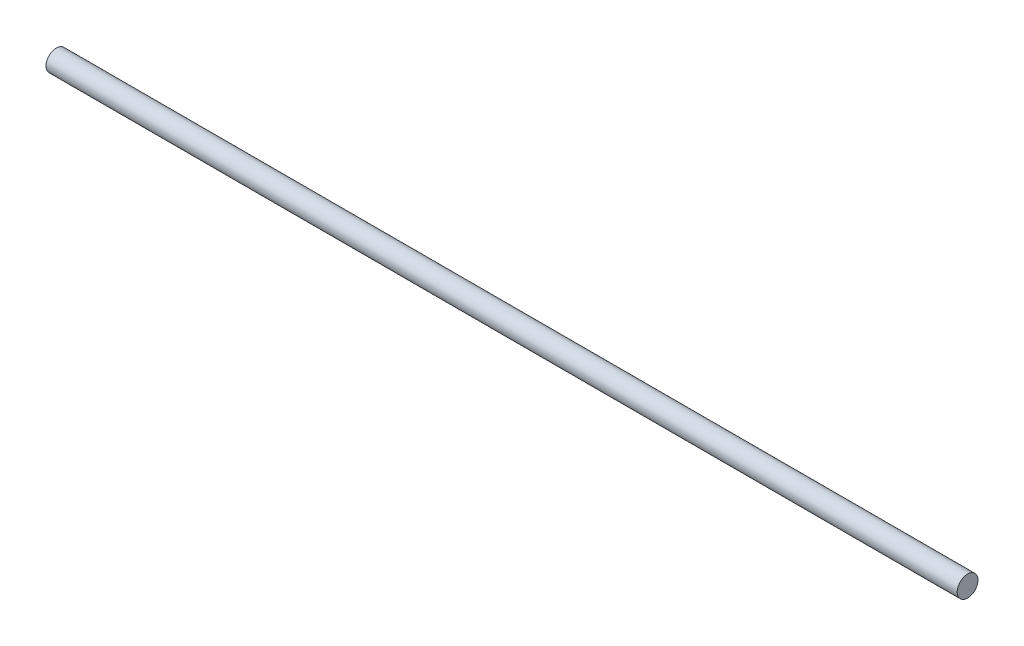
SolidWorks part; units mm, degrees
ref_plane "Front Plane" through (0, 0, 0) normal (0, 0, 1) x (1, 0, 0)
ref_plane "Top Plane" through (0, 0, 0) normal (0, 1, 0) x (1, 0, 0)
ref_plane "Right Plane" through (0, 0, 0) normal (1, 0, 0) x (0, 0, -1)
sketch "Sketch1" plane through (0, 0, 0) normal (1, 0, 0) x (0, 0, -1)
  circle A0 centre (0, 0) radius 4
  dimension "D1" = 8
extrude "Boss-Extrude1" add sketch "Sketch1" along normal mid plane 350
